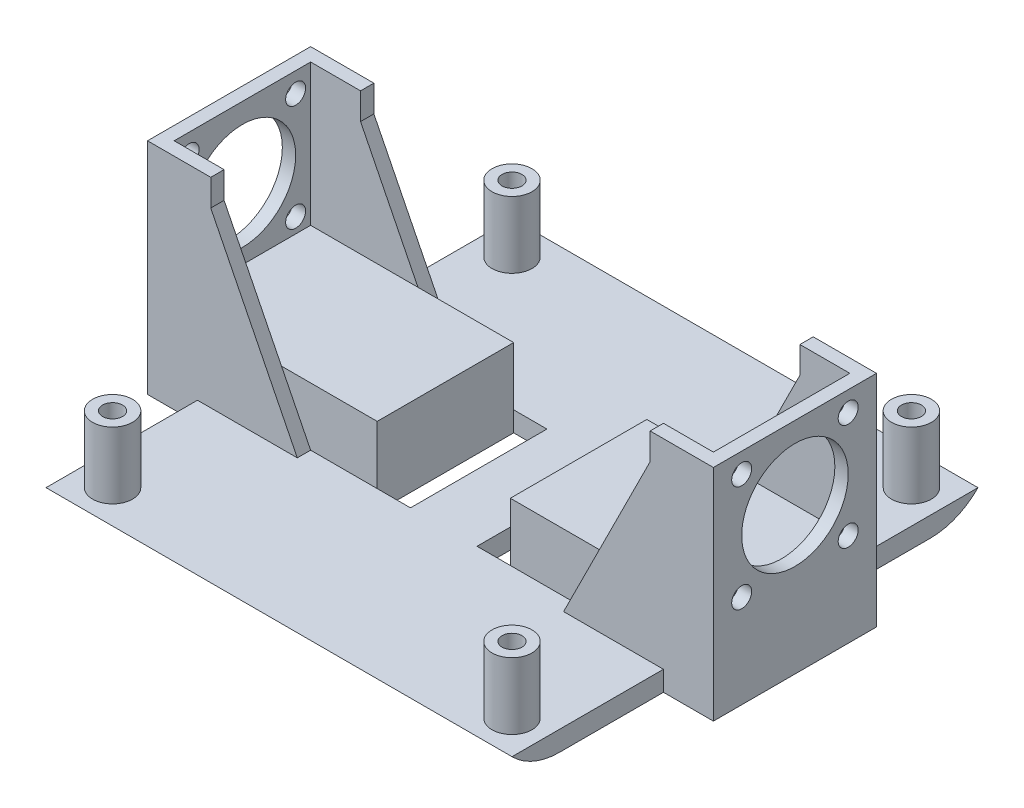
SolidWorks part; units mm, degrees
ref_plane "Front Plane" through (0, 0, 0) normal (0, 0, 1) x (1, 0, 0)
ref_plane "Top Plane" through (0, 0, 0) normal (0, 1, 0) x (1, 0, 0)
ref_plane "Right Plane" through (0, 0, 0) normal (1, 0, 0) x (0, 0, -1)
sketch "Sketch1" plane through (0, 0, 0) normal (0, 1, 0) x (1, 0, 0)
  line L1 (0, 0) -> (70, 0)
  line L2 (0, 0) -> (0, 70)
  line L3 (0, 70) -> (70, 70)
  line L4 (70, 0) -> (70, 70)
  dimension "D1" = 70
extrude "Boss-Extrude1" add sketch "Sketch1" along normal blind 3
sketch "Sketch2" plane through (0, 3, 0) normal (0, 1, 0) x (1, 0, 0)
  line L0 (0, 70) -> (0, 0) construction
  line L1 (0, 24.75) -> (-7.5, 24.75)
  line L2 (0, 24.75) -> (0, 45.25)
  line L3 (0, 45.25) -> (-7.5, 45.25)
  line L4 (-7.5, 24.75) -> (-7.5, 45.25)
  line L5 (70, 0) -> (70, 70) construction
  line L6 (70, 24.75) -> (77.5, 24.75)
  line L7 (70, 24.75) -> (70, 45.25)
  line L8 (70, 45.25) -> (77.5, 45.25)
  line L9 (77.5, 24.75) -> (77.5, 45.25)
  line L10 (-7.5, 45.25) -> (7.5, 45.25) construction
  line L11 (77.5, 45.25) -> (62.5, 45.25) construction
  point P13 (70, 35)
  point P14 (70, 35)
  point P15 (0, 35)
  point P16 (0, 35)
  dimension "D1" = 15
  dimension "D2" = 55
  dimension "D3" = 20.5
extrude "Boss-Extrude2" add sketch "Sketch2" against normal up to surface (3 mm away) up to face at (35, 0, -35)
sketch "Sketch3" plane through (0, 3, 0) normal (0, 1, 0) x (1, 0, 0)
  line L0 (-7.5, 24.75) -> (0, 24.75) construction
  line L1 (-7.5, 45.25) -> (-5.5, 45.25)
  line L2 (-7.5, 45.25) -> (-7.5, 24.75)
  line L3 (-7.5, 24.75) -> (-5.5, 24.75)
  line L4 (-5.5, 45.25) -> (-5.5, 24.75)
  line L5 (77.5, 45.25) -> (70, 45.25) construction
  line L6 (77.5, 24.75) -> (75.5, 24.75)
  line L7 (77.5, 24.75) -> (77.5, 45.25)
  line L8 (77.5, 45.25) -> (75.5, 45.25)
  line L9 (75.5, 24.75) -> (75.5, 45.25)
  dimension "D1" = 2
extrude "Boss-Extrude3" add sketch "Sketch3" along normal blind 30
sketch "Sketch4" plane through (-5.5, 0, 0) normal (1, 0, 0) x (0, 0, -1)
  line L0 (24.75, 12) -> (45.25, 12) construction
  line L1 (24.75, 33) -> (24.75, 3) construction
  line L2 (45.25, 33) -> (45.25, 3) construction
  line L5 (24.75, 33) -> (45.25, 33) construction
  line L6 (27, 14) -> (43, 14) construction
  line L7 (43, 14) -> (43, 30) construction
  circle A0 centre (35, 22) radius 8
  circle A1 centre (43, 30) radius 1.5
  circle A2 centre (43, 14) radius 1.5
  circle A3 centre (27, 30) radius 1.5
  circle A4 centre (27, 14) radius 1.5
  point P6 (55.25, 11.6238)
  point P13 (35, 33)
  point P21 (43, 22)
  point P23 (35, 14)
  point P24 (35, 12)
  dimension "D2" = 16
  dimension "D7" = 3
  dimension "D1" = 9
  dimension "D3" = 10
  dimension "D4" = 16
  dimension "D5" = 16
  dimension "D6" = 10
extrude "Cut-Extrude1" cut sketch "Sketch4" against normal through all both and the other way through all
sketch "Sketch5" plane through (0, 3, 0) normal (0, 1, 0) x (1, 0, 0)
  line L0 (-7.5, 45.25) -> (-7.5, 24.75) construction
  line L1 (2, 24.75) -> (-7.5, 24.75)
  line L2 (2, 24.75) -> (2, 22.75)
  line L3 (2, 22.75) -> (-7.5, 22.75)
  line L4 (-7.5, 24.75) -> (-7.5, 22.75)
  line L5 (-5.5, 35) -> (77.5, 35) construction
  line L6 (-5.5, 24.75) -> (-5.5, 45.25) construction
  line L7 (77.5, 24.75) -> (77.5, 45.25) construction
  line L8 (77.5, 24.75) -> (77.5, 45.25)
  line L9 (35, 0) -> (35, 70) construction
  line L10 (0, 0) -> (70, 0) construction
  line L11 (70, 70) -> (0, 70) construction
  line L12 (2, 47.25) -> (-7.5, 47.25)
  line L13 (-7.5, 45.25) -> (-7.5, 47.25)
  line L14 (2, 45.25) -> (-7.5, 45.25)
  line L15 (2, 45.25) -> (2, 47.25)
  line L16 (68, 22.75) -> (77.5, 22.75)
  line L17 (77.5, 24.75) -> (77.5, 22.75)
  line L18 (68, 24.75) -> (77.5, 24.75)
  line L19 (68, 24.75) -> (68, 22.75)
  line L20 (68, 45.25) -> (68, 47.25)
  line L21 (68, 45.25) -> (77.5, 45.25)
  line L22 (77.5, 45.25) -> (77.5, 47.25)
  line L23 (68, 47.25) -> (77.5, 47.25)
  line L24 (-5.5, 24.75) -> (0, 24.75) construction
  dimension "D1" = 2
  dimension "D2" = 2
extrude "Boss-Extrude4" add sketch "Sketch5" against normal up to surface and the other way up to surface contours L12 L13 L14 L15 | L2 L1 L4 L3 | L20 L23 L22 L21 | L16 L17 L18 L19 up to face at (35, 0, -35) other way up to face at (76.5, 33, -35)
sketch "Sketch6" plane through (0, 0, -47.25) normal (0, 0, -1) x (-1, 0, 0)
  line L0 (-70, 33) -> (-55, 3)
  line L2 (-55, 3) -> (-70, 3)
  line L3 (-70, 3) -> (-70, 33)
  line L4 (0, 33) -> (-15, 3)
  line L5 (-15, 3) -> (0, 3)
  line L6 (0, 3) -> (0, 33)
  line L7 (-68, 33) -> (-77.5, 33) construction
  line L8 (-2, 33) -> (7.5, 33) construction
  dimension "D1" = 15
extrude "Boss-Extrude5" add sketch "Sketch6" against normal up to surface (24.5 mm away) up to face at (71.8333, 12, -22.75)
sketch "Sketch7" plane through (0, 3, 0) normal (0, 1, 0) x (1, 0, 0)
  line L1 (75.5, 24.75) -> (-5.5, 24.75)
  line L2 (75.5, 24.75) -> (75.5, 45.25)
  line L3 (75.5, 45.25) -> (-5.5, 45.25)
  line L4 (-5.5, 24.75) -> (-5.5, 45.25)
extrude "Cut-Extrude2" cut sketch "Sketch7" along normal through all
sketch "Sketch8" plane through (0, 3, 0) normal (0, 1, 0) x (1, 0, 0)
  line L0 (15, 45.25) -> (-5.5, 45.25) construction
  line L1 (25, 45.25) -> (30, 45.25)
  line L2 (25, 45.25) -> (25, 24.75)
  line L3 (25, 24.75) -> (30, 24.75)
  line L4 (30, 45.25) -> (30, 24.75)
  line L5 (40, 45.25) -> (45, 45.25)
  line L6 (40, 45.25) -> (40, 24.75)
  line L7 (40, 24.75) -> (45, 24.75)
  line L8 (45, 45.25) -> (45, 24.75)
  line L9 (-5.5, 24.75) -> (15, 24.75) construction
  line L10 (25, 45.25) -> (15, 45.25) construction
  line L11 (45, 45.25) -> (55, 45.25) construction
  line L12 (-5.5, 24.75) -> (-5.5, 45.25) construction
  dimension "D1" = 30.5
  dimension "D2" = 5
extrude "Cut-Extrude3" cut sketch "Sketch8" against normal through all
sketch "Sketch17" plane through (75.5, 0, 0) normal (-1, 0, 0) x (0, 0, 1)
  line L0 (-45.25, 33) -> (-45.25, 3) construction
  line L1 (-24.75, 3) -> (-45.25, 3)
  line L2 (-24.75, 3) -> (-24.75, 11.75)
  line L3 (-24.75, 11.75) -> (-45.25, 11.75)
  line L4 (-45.25, 3) -> (-45.25, 11.75)
  circle A0 centre (-27, 14) radius 1.5 construction
  circle A1 centre (-27, 14) radius 1.5
  line M6 (-45.25, 3) -> (-24.75, 3)
  line M7 (-24.75, 3) -> (-24.75, 33)
  line M9 (-45.25, 33) -> (-45.25, 3)
  dimension "D1" = 2.25
extrude "Boss-Extrude7" add sketch "Sketch17" along normal up to surface (30.5 mm away) contours L3 M7 M9 M6 region at (75.5, 7.375, -35) up to face at (45, 1.5, -35)
sketch "Sketch18" plane through (-5.5, 0, 0) normal (1, 0, 0) x (0, 0, -1)
  line L6 (24.75, 3) -> (24.75, 0)
  line L7 (24.75, 11.75) -> (24.75, 3)
  line L8 (45.25, 11.75) -> (24.75, 11.75)
  line L9 (45.25, 3) -> (45.25, 11.75)
  line L10 (45.25, 0) -> (45.25, 3)
  line L11 (24.75, 0) -> (45.25, 0)
  line L12 (24.75, 3) -> (24.75, 0)
  line L13 (24.75, 11.75) -> (24.75, 3)
  line L14 (45.25, 11.75) -> (24.75, 11.75)
  line L15 (45.25, 3) -> (45.25, 11.75)
  line L16 (45.25, 0) -> (45.25, 3)
  line L17 (24.75, 0) -> (45.25, 0)
  point P2 (0, 0)
  dimension "D1" = 0
extrude "Boss-Extrude8" add sketch "Sketch18" along normal up to surface (30.5 mm away) up to face at (25, 1.5, -35)
sketch "Sketch19" plane through (0, 3, 0) normal (0, 1, 0) x (1, 0, 0)
  line L0 (65, 5) -> (65, 65) construction
  line L1 (65, 65) -> (5, 65) construction
  line L2 (5, 65) -> (5, 5) construction
  line L3 (5, 5) -> (65, 5) construction
  line L4 (0, 70) -> (0, 47.25) construction
  line L5 (70, 70) -> (0, 70) construction
  line L6 (70, 0) -> (70, 22.75) construction
  line L7 (0, 0) -> (70, 0) construction
  circle A0 centre (5, 5) radius 3
  circle A1 centre (65, 5) radius 3
  circle A2 centre (65, 65) radius 3
  circle A3 centre (5, 65) radius 3
  dimension "D5" = 6
  dimension "D1" = 5
  dimension "D2" = 5
  dimension "D3" = 5
  dimension "D4" = 5
extrude "Boss-Extrude9" add sketch "Sketch19" along normal blind 10
sketch "Sketch20" plane through (0, 13, 0) normal (0, 1, 0) x (1, 0, 0)
  circle A0 centre (5, 65) radius 1.5
  circle A1 centre (65, 65) radius 1.5
  circle A2 centre (65, 5) radius 1.5
  circle A3 centre (5, 5) radius 1.5
  point P12 (0, 0)
  dimension "D1" = 3
extrude "Cut-Extrude4" cut sketch "Sketch20" against normal through all
fillet "Fillet1" radius 10 2 edges at (35, 0, 0) (35, 0, -70)
